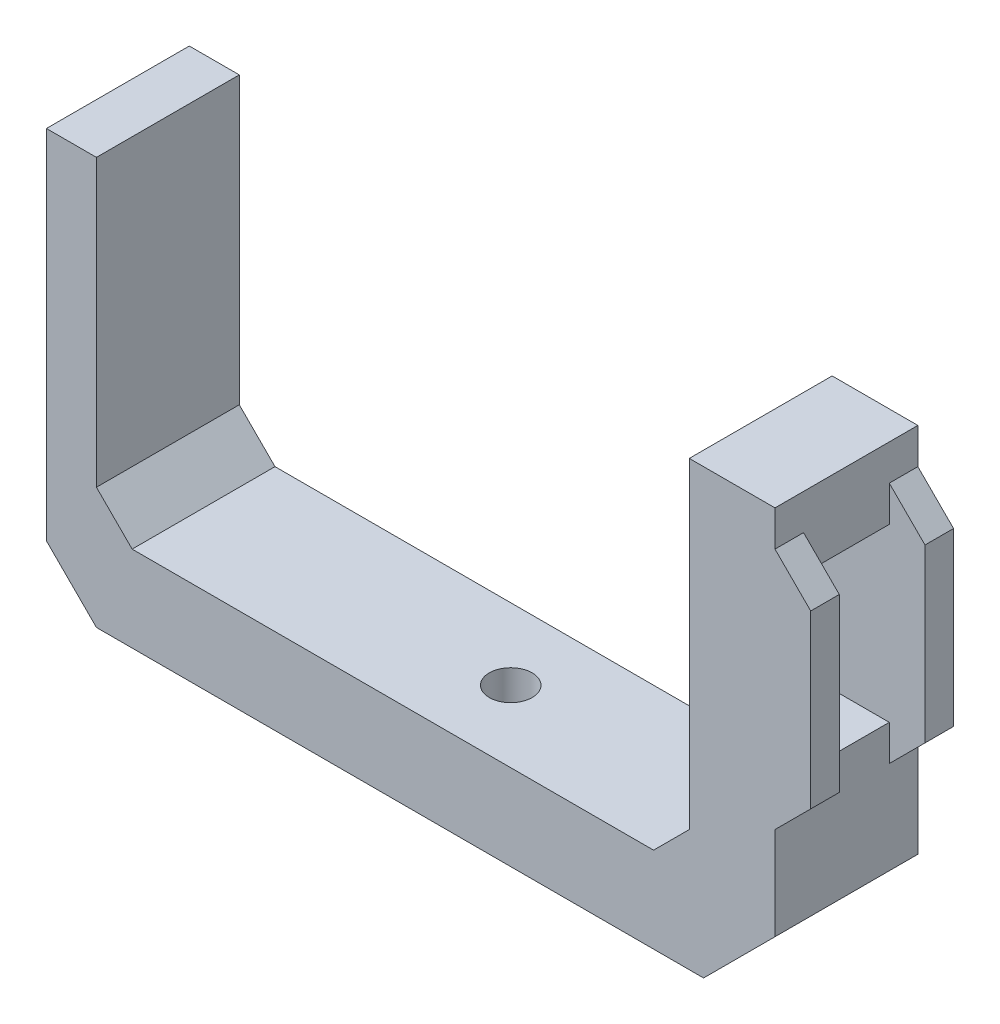
SolidWorks part; units mm, degrees
ref_plane "Front Plane" through (0, 0, 0) normal (0, 0, 1) x (1, 0, 0)
ref_plane "Top Plane" through (0, 0, 0) normal (0, 1, 0) x (1, 0, 0)
ref_plane "Right Plane" through (0, 0, 0) normal (1, 0, 0) x (0, 0, -1)
sketch "Sketch1" plane through (0, 0, 0) normal (0, 0, 1) x (1, 0, 0)
  line L1 (16.2, 38.12) -> (28.2, 38.12)
  line L2 (-28.8, -11.88) -> (-28.8, -23.88)
  line L3 (-28.8, -23.88) -> (28.2, -23.88)
  line L4 (28.2, 38.12) -> (28.2, -23.88)
  line L7 (-28.8, -11.88) -> (16.2, -11.88)
  line L8 (16.2, 38.12) -> (16.2, -11.88)
  dimension "D1" = 12
  dimension "D2" = 12
  dimension "D3" = 45
  dimension "D4" = 50
extrude "Boss-Extrude1" add sketch "Sketch1" along normal blind 20
chamfer "Chamfer1" distance 5 angle 45 1 edges at (16.2, -11.88, 10)
chamfer "Chamfer2" distance 10 angle 45 1 edges at (28.2, -23.88, 10)
sketch "Sketch2" plane through (0, -11.88, 0) normal (0, 1, 0) x (1, 0, 0)
  line L0 (11.2, -20) -> (11.2, 0) construction
  circle A0 centre (-18.8, -10) radius 1.75
  dimension "D1" = 3.5
  dimension "D2" = 30
extrude "Cut-Extrude1" cut sketch "Sketch2" against normal blind 20
sketch "Sketch3" plane through (0, -11.88, 0) normal (0, 1, 0) x (1, 0, 0)
  circle A0 centre (-18.8, -10) radius 3
  dimension "D1" = 6
extrude "Cut-Extrude2" cut sketch "Sketch3" against normal blind 10
sketch "Sketch4" plane through (0, -21.88, 0) normal (0, 1, 0) x (1, 0, 0)
  circle A0 centre (-18.8, -10) radius 3
extrude "Boss-Extrude2" add sketch "Sketch4" along normal blind 2
sketch "Sketch5" plane through (0, -19.88, 0) normal (0, 1, 0) x (1, 0, 0)
  circle A0 centre (-18.8, -10) radius 1
  dimension "D1" = 2
extrude "Cut-Extrude3" cut sketch "Sketch5" against normal blind 2
sketch "Sketch6" plane through (16.2, 0, 0) normal (-1, 0, 0) x (0, 0, 1)
  line L0 (0, 38.12) -> (0, -6.88) construction
  line L1 (4, 28.12) -> (16, 28.12)
  line L2 (4, 28.12) -> (4, 4.12)
  line L3 (4, 4.12) -> (16, 4.12)
  line L4 (16, 28.12) -> (16, 4.12)
  line L5 (0, -6.88) -> (20, -6.88) construction
  dimension "D1" = 12
  dimension "D2" = 24
  dimension "D3" = 4
  dimension "D4" = 35
extrude "Cut-Extrude4" cut sketch "Sketch6" against normal blind 12
sketch "Sketch7" plane through (28.2, 0, 0) normal (1, 0, 0) x (0, 0, -1)
  line L0 (-20, -13.88) -> (-20, 38.12) construction
  line L1 (-16, 28.12) -> (-20, 28.12)
  line L2 (-16, 28.12) -> (-16, 4.12)
  line L3 (-16, 4.12) -> (-20, 4.12)
  line L4 (-20, 28.12) -> (-20, 4.12)
  line L5 (0, -13.88) -> (0, 38.12) construction
  line L6 (-4, 28.12) -> (0, 28.12)
  line L7 (-4, 28.12) -> (-4, 4.12)
  line L8 (-4, 4.12) -> (0, 4.12)
  line L9 (0, 28.12) -> (0, 4.12)
extrude "Boss-Extrude3" add sketch "Sketch7" along normal blind 5
chamfer "Chamfer3" distance 5 angle 45 4 edges at (28.2, 4.12, 18) (28.2, 4.12, 2) (28.2, 28.12, 18) (28.2, 28.12, 2)
sketch "Sketch8" plane through (-28.8, 0, 0) normal (-1, 0, 0) x (0, 0, 1)
  line L1 (0, -11.88) -> (20, -11.88)
  line L2 (0, -11.88) -> (0, -23.88)
  line L3 (0, -23.88) -> (20, -23.88)
  line L4 (20, -11.88) -> (20, -23.88)
extrude "Boss-Extrude4" add sketch "Sketch8" along normal blind 45
sketch "Sketch9" plane through (0, -11.88, 0) normal (0, 1, 0) x (1, 0, 0)
  line L0 (11.2, 0) -> (-73.8, 0) construction
  line L1 (-73.8, -20) -> (-66.8, -20)
  line L2 (-73.8, -20) -> (-73.8, 0)
  line L3 (-73.8, 0) -> (-66.8, 0)
  line L4 (-66.8, -20) -> (-66.8, 0)
  dimension "D1" = 7
extrude "Boss-Extrude5" add sketch "Sketch9" along normal blind 45
chamfer "Chamfer4" distance 5 angle 45 1 edges at (-66.8, -11.88, 10)
chamfer "Chamfer5" distance 7 angle 45 1 edges at (-73.8, -23.88, 10)
